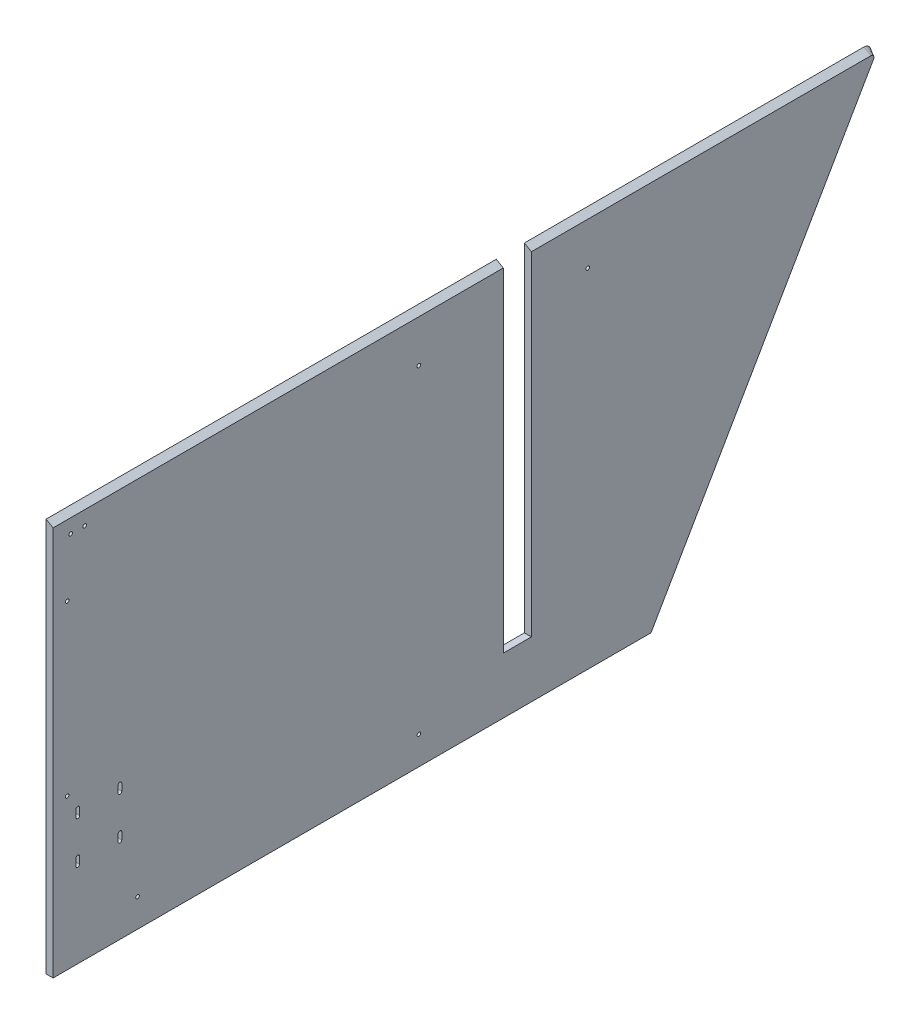
SolidWorks part; units mm, degrees
material "Acrylic (Medium-high impact)"
ref_plane "Front Plane" through (0, 0, 0) normal (0, 0, 1) x (1, 0, 0)
ref_plane "Top Plane" through (0, 0, 0) normal (0, 1, 0) x (1, 0, 0)
ref_plane "Right Plane" through (0, 0, 0) normal (1, 0, 0) x (0, 0, -1)
sketch "Sketch1" plane through (0, 0, 0) normal (1, 0, 0) x (0, 0, -1)
  line L0 (588.6358, 323.8269) -> (383.33, -31.7731)
  line L1 (-160.6642, 323.8269) -> (588.6358, 323.8269)
  line L2 (-160.6642, 323.8269) -> (-160.6642, -31.7731)
  line L3 (-160.6642, -31.7731) -> (383.33, -31.7731)
  dimension "D1" = 355.6
  dimension "D2" = 749.3
  dimension "D3" = 120
extrude "Boss-Extrude1" add sketch "Sketch1" along normal blind 6.35
sketch "Sketch2" plane through (0, 0, 0) normal (-1, 0, 0) x (0, 0, 1)
  line L0 (-588.6358, 323.8269) -> (160.6642, 323.8269) construction
  line L1 (-271.1358, 323.8269) -> (-245.7358, 323.8269)
  line L2 (-271.1358, 323.8269) -> (-271.1358, 19.0269)
  line L3 (-271.1358, 19.0269) -> (-245.7358, 19.0269)
  line L4 (-245.7358, 323.8269) -> (-245.7358, 19.0269)
  line L5 (160.6642, 323.8269) -> (160.6642, -31.7731) construction
  dimension "D1" = 25.4
  dimension "D2" = 304.8
  dimension "D3" = 406.4
extrude "Cut-Extrude1" cut sketch "Sketch2" against normal through all
fillet "Fillet1" radius 6.35 1 edges at (3.175, 323.8269, -588.6358)
chamfer "Chamfer3" distance 6.35 angle 30 4 edges at (6.35, 323.8269, -42.5358) (6.35, 141.2644, -483.2333) (6.35, 320.6519, -583.1365) (6.35, 323.8269, -424.3865) first distance on face at (3.175, 323.8269, -42.5358) first distance on face at (3.175, 141.2644, -483.2333) first distance on face at (3.175, 319.8581, -581.7617) first distance on face at (3.175, 323.8269, -424.3865)
hole_wizard "CSK for #4 Flat Head Machine Screw1" positions "3DSketch1" profile "Sketch3" countersink size "#4" standard "ANSI Inch" end condition through all
sketch3d "3DSketch1"
  line L1 (0, 323.8269, 160.6642) -> (0, -31.7731, 160.6642) construction
  line L3 (0, -31.7731, 160.6642) -> (0, -31.7731, -383.33) construction
  point P0 (0, 256.5169, 147.9642)
  point P2 (0, 281.9169, -169.5358)
  point P4 (0, 281.9169, -321.9358)
  point P14 (0, 104.1169, 147.9642)
  point P19 (0, -6.3731, 84.4642)
  point P21 (0, -6.3731, -169.5358)
  dimension "D2" = 288.29
  dimension "D6" = 313.69
  dimension "D3" = 330.2
  dimension "D13" = 313.69
  dimension "D4" = 12.7
  dimension "D5" = 482.6
  dimension "D11" = 76.2
  dimension "D7" = 135.89
  dimension "D8" = 25.4
  dimension "D9" = 12.7
  dimension "D10" = 25.4
  dimension "D12" = 330.2
sketch "Sketch3" plane through (0, 256.5169, 147.9642) normal (0, 1, 0) x (0, 0, 1)
  line L0 (0, 0) -> (0, 6.35)
  line L1 (0, 6.35) -> (1.6319, 6.35)
  line L2 (1.6319, 6.35) -> (1.6319, 1.4098)
  line L3 (1.6319, 1.4098) -> (2.8575, 0)
  line L5 (2.8575, 0) -> (0, 0)
  line L6 (-1.6319, 1.4098) -> (-2.8575, 0) construction
  line L11 (0, -6.35) -> (0, 107.95) construction
  dimension "Thru Hole Dia." = 3.2639
  dimension "Thru Hole Depth" = 6.35
  dimension "Near C'Sink Dia." = 5.715
  dimension "Near C'Sink Angle" = 82
sketch "Sketch7" plane through (0, 0, 0) normal (-1, 0, 0) x (0, 0, 1)
  line L0 (138.4392, 89.636) -> (138.4392, 83.286) construction
  line L1 (140.0712, 89.636) -> (140.0712, 83.286)
  line L2 (136.8073, 89.636) -> (136.8073, 83.286)
  line L3 (100.3392, 83.286) -> (100.3392, 89.636) construction
  line L4 (98.7073, 83.286) -> (98.7073, 89.636)
  line L5 (101.9712, 83.286) -> (101.9712, 89.636)
  line L6 (100.3392, 45.186) -> (100.3392, 51.536) construction
  line L7 (98.7073, 45.186) -> (98.7073, 51.536)
  line L8 (101.9712, 45.186) -> (101.9712, 51.536)
  line L9 (138.4392, 45.186) -> (138.4392, 51.536) construction
  line L10 (136.8073, 45.186) -> (136.8073, 51.536)
  line L11 (140.0712, 45.186) -> (140.0712, 51.536)
  arc A0 (140.0712, 89.636) -> (136.8073, 89.636) centre (138.4392, 89.636) ccw
  arc A1 (136.8073, 83.286) -> (140.0712, 83.286) centre (138.4392, 83.286) ccw
  arc A2 (98.7073, 83.286) -> (101.9712, 83.286) centre (100.3392, 83.286) ccw
  arc A3 (101.9712, 89.636) -> (98.7073, 89.636) centre (100.3392, 89.636) ccw
  arc A4 (98.7073, 45.186) -> (101.9712, 45.186) centre (100.3392, 45.186) ccw
  arc A5 (101.9712, 51.536) -> (98.7073, 51.536) centre (100.3392, 51.536) ccw
  arc A6 (136.8073, 45.186) -> (140.0712, 45.186) centre (138.4392, 45.186) ccw
  arc A7 (140.0712, 51.536) -> (136.8073, 51.536) centre (138.4392, 51.536) ccw
  point P2 (138.4392, 86.461)
  point P10 (100.3392, 86.461)
  point P17 (100.3392, 48.361)
  point P26 (138.4392, 48.361)
  dimension "D1" = 6.35
  dimension "D2" = 3.2639
  dimension "D3" = 6.35
  dimension "D4" = 3.2639
  dimension "D5" = 3.2639
  dimension "D6" = 3.2639
  dimension "D7" = 6.35
  dimension "D8" = 6.35
extrude "Cut-Extrude2" cut sketch "Sketch7" against normal up to next
hole_wizard "CSK for #4 Flat Head Machine Screw2" positions "Sketch9" profile "Sketch8" countersink size "#4" standard "ANSI Inch" end condition through all
sketch "Sketch9" plane through (0, 0, 0) normal (-1, 0, 0) x (0, 0, 1)
  circle A0 centre (144.7892, 307.4607) radius 1.1303 construction
  circle A1 centre (132.0892, 307.4607) radius 1.1303 construction
  point P0 (132.0892, 307.4607)
  point P2 (144.7892, 307.4607)
sketch "Sketch8" plane through (0, 307.4607, 132.0892) normal (0, 1, 0) x (0, 0, 1)
  line L0 (0, 0) -> (0, 6.35)
  line L1 (0, 6.35) -> (1.6319, 6.35)
  line L2 (1.6319, 6.35) -> (1.6319, 1.4098)
  line L3 (1.6319, 1.4098) -> (2.8575, 0)
  line L5 (2.8575, 0) -> (0, 0)
  line L6 (-1.6319, 1.4098) -> (-2.8575, 0) construction
  line L11 (0, -6.35) -> (0, 107.95) construction
  dimension "Thru Hole Dia." = 3.2639
  dimension "Thru Hole Depth" = 6.35
  dimension "Near C'Sink Dia." = 5.715
  dimension "Near C'Sink Angle" = 82
